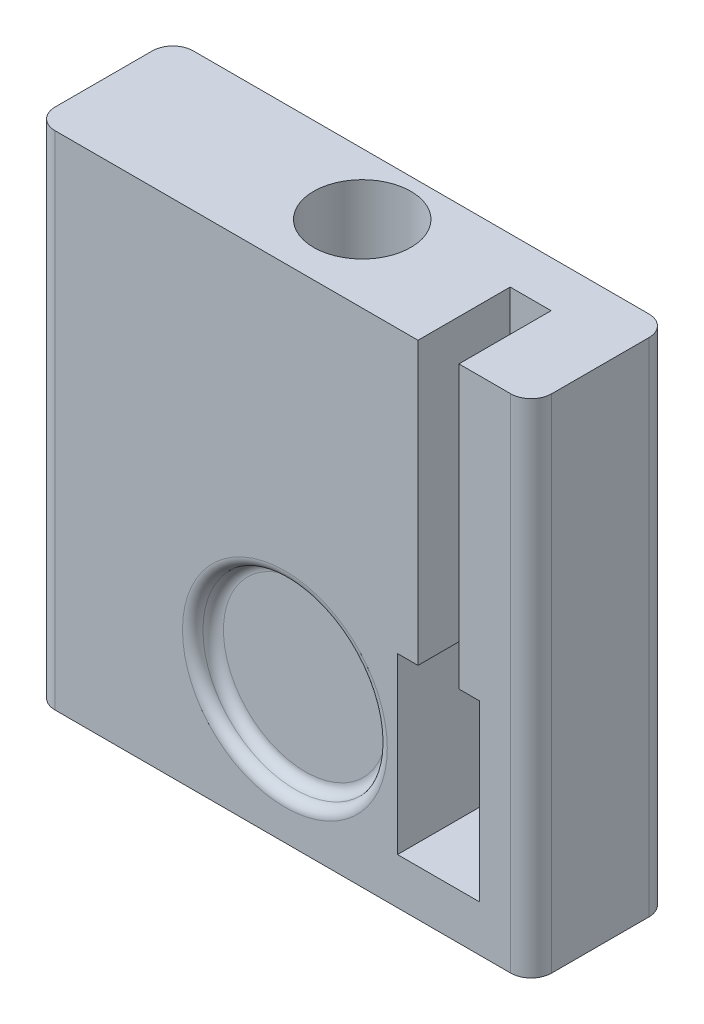
SolidWorks part; units mm, degrees
ref_plane "前视基准面" through (0, 0, 0) normal (0, 0, 1) x (1, 0, 0)
ref_plane "上视基准面" through (0, 0, 0) normal (0, 1, 0) x (1, 0, 0)
ref_plane "右视基准面" through (0, 0, 0) normal (1, 0, 0) x (0, 0, -1)
sketch "草图1" plane through (0, 30.0147, 0) normal (0, -1, 0) x (1, 0, 0)
  line L0 (43.6967, -16.841) -> (-0.8033, -16.841) construction
  line L1 (43.6967, -16.841) -> (-0.8033, -16.841)
  line L2 (45.6967, -28.341) -> (45.6967, -18.841) construction
  line L3 (45.6967, -28.341) -> (45.6967, -18.841)
  line L4 (-0.8033, -30.341) -> (43.6967, -30.341) construction
  line L5 (-0.8033, -30.341) -> (43.6967, -30.341)
  line L6 (-2.8033, -18.841) -> (-2.8033, -28.341) construction
  line L7 (-2.8033, -18.841) -> (-2.8033, -28.341)
  arc A0 (45.6967, -18.841) -> (43.6967, -16.841) centre (43.6967, -18.841) ccw construction
  arc A1 (45.6967, -18.841) -> (43.6967, -16.841) centre (43.6967, -18.841) ccw
  arc A2 (43.6967, -30.341) -> (45.6967, -28.341) centre (43.6967, -28.341) ccw construction
  arc A3 (43.6967, -30.341) -> (45.6967, -28.341) centre (43.6967, -28.341) ccw
  arc A4 (-0.8033, -16.841) -> (-2.8033, -18.841) centre (-0.8033, -18.841) ccw construction
  arc A5 (-0.8033, -16.841) -> (-2.8033, -18.841) centre (-0.8033, -18.841) ccw
  arc A6 (-2.8033, -28.341) -> (-0.8033, -30.341) centre (-0.8033, -28.341) ccw construction
  arc A7 (-2.8033, -28.341) -> (-0.8033, -30.341) centre (-0.8033, -28.341) ccw
extrude "凸台-拉伸1" add sketch "草图1" along normal up to surface (49 mm away)
sketch "草图2" plane through (0, 0, -16.841) normal (0, 0, 1) x (1, 0, 0)
  line L1 (32.6433, 2.5167) -> (40.6433, 2.5167)
  line L2 (32.6433, 2.5167) -> (32.6433, -14.4833)
  line L3 (32.6433, -14.4833) -> (40.6433, -14.4833)
  line L4 (40.6433, 2.5167) -> (40.6433, -14.4833)
  dimension "D1" = 17
  dimension "D2" = 8
extrude "切除-拉伸1" cut sketch "草图2" against normal blind 10
sketch "草图3" plane through (0, 0, -16.841) normal (0, 0, 1) x (1, 0, 0)
  line L0 (40.6433, 2.5167) -> (32.6433, 2.5167) construction
  circle A0 centre (21.6433, -5.9833) radius 9
  point P4 (36.6433, 2.5167)
  dimension "D1" = 18
  dimension "D2" = 15
extrude "切除-拉伸2" cut sketch "草图3" against normal blind 2
fillet "圆角1" radius 1 2 edges at (30.6433, -5.9833, -16.841) (30.6433, -5.9833, -18.841)
sketch "草图4" plane through (0, 30.0147, 0) normal (0, 1, 0) x (1, 0, 0)
  line L0 (-0.8033, 30.341) -> (43.6967, 30.341) construction
  line L1 (45.6967, 28.341) -> (45.6967, 18.841) construction
  circle A0 centre (21.6967, 24.341) radius 4.75
  dimension "D1" = 9.5
  dimension "D2" = 6
  dimension "D3" = 24
extrude "切除-拉伸4" cut sketch "草图4" against normal blind 40
sketch "草图5" plane through (0, 30.0147, 0) normal (0, 1, 0) x (1, 0, 0)
  line L0 (32.6433, 26.841) -> (40.6433, 26.841) construction
  line L1 (32.6433, 26.841) -> (40.6433, 26.841)
  line L2 (43.6967, 16.841) -> (-0.8033, 16.841) construction
  line L3 (34.6433, 36.841) -> (38.6433, 36.841)
  line L4 (34.6433, 36.841) -> (34.6433, 16.841)
  line L5 (34.6433, 16.841) -> (38.6433, 16.841)
  line L6 (38.6433, 36.841) -> (38.6433, 16.841)
  line L7 (34.6433, 36.841) -> (38.6433, 16.841) construction
  line L8 (34.6433, 16.841) -> (38.6433, 36.841) construction
  point P2 (36.6433, 26.841)
  line M10 (-0.8033, 16.841) -> (43.6967, 16.841)
  dimension "D1" = 4
extrude "切除-拉伸5" cut sketch "草图5" against normal blind 38 contours L6 L1 L4 M10 region at (36.6433, 30.0147, -21.841)
sketch "草图6" plane through (0, 30.0147, 0) normal (0, 1, 0) x (1, 0, 0)
  line L0 (38.6433, 26.841) -> (38.6433, 16.841) construction
  line L1 (34.6433, 26.841) -> (38.6433, 26.841)
  line L2 (34.6433, 26.841) -> (34.6433, 25.841)
  line L3 (34.6433, 25.841) -> (38.6433, 25.841)
  line L4 (38.6433, 26.841) -> (38.6433, 25.841)
  dimension "D1" = 1
extrude "凸台-拉伸2" add sketch "草图6" against normal up to surface (27.498 mm away) up to face at (39.6433, 2.5167, -21.841)
